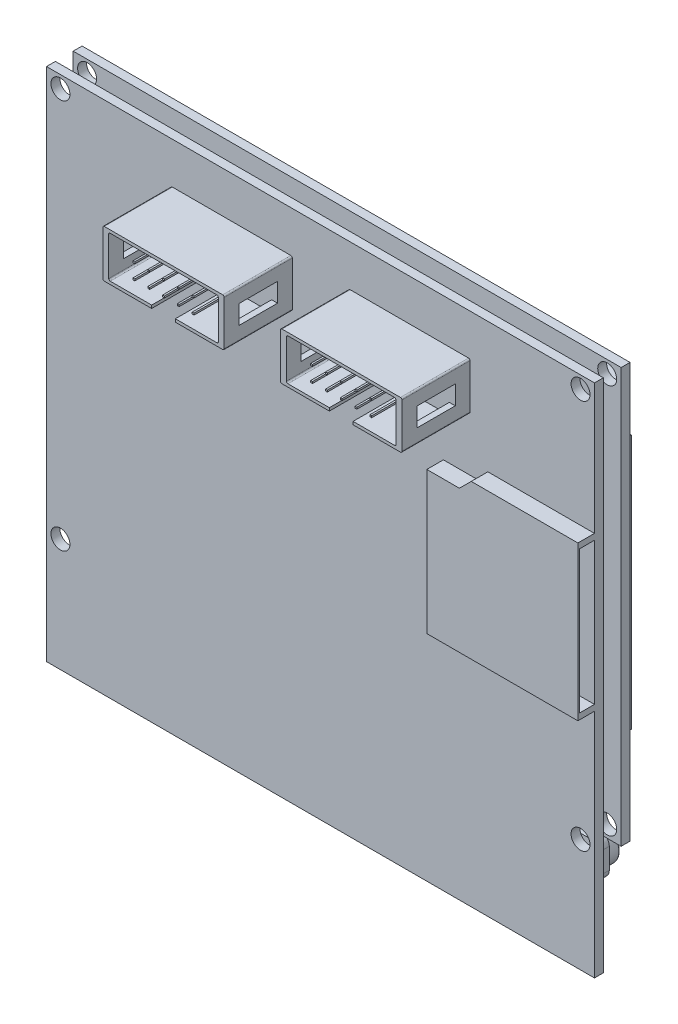
SolidWorks part; units mm, degrees
material "ABS"
ref_plane "Front Plane" through (0, 0, 0) normal (0, 0, 1) x (1, 0, 0)
ref_plane "Top Plane" through (0, 0, 0) normal (0, 1, 0) x (1, 0, 0)
ref_plane "Right Plane" through (0, 0, 0) normal (1, 0, 0) x (0, 0, -1)
sketch "Skica1" plane through (0, 0, 0) normal (0, 0, 1) x (1, 0, 0)
  line L1 (0, 0) -> (92.5, 0)
  line L2 (0, 0) -> (0, 87)
  line L3 (0, 87) -> (92.5, 87)
  line L4 (92.5, 0) -> (92.5, 87)
  dimension "D1" = 87
  dimension "D2" = 92.5
extrude "Přidat vysunutím1" add sketch "Skica1" along normal blind 1.5
ref_plane "Rovina1" through (0, 0, -3) normal (0, 0, -1) x (-1, 0, 0)
sketch "Skica2" plane through (0, 0, -3) normal (0, 0, -1) x (-1, 0, 0)
  line L0 (0, 87) -> (0, 0) construction
  line L1 (-92.5, 87) -> (0, 87)
  line L2 (-92.5, 87) -> (-92.5, 17)
  line L3 (-92.5, 17) -> (0, 17)
  line L4 (0, 87) -> (0, 17)
  dimension "D1" = 70
extrude "Přidat vysunutím2" add sketch "Skica2" along normal blind 1.5 separate body
sketch "Skica3" plane through (0, 0, -4.5) normal (0, 0, -1) x (-1, 0, 0)
  line L0 (-46.25, 87) -> (-46.25, 17) construction
  line L1 (0, 87) -> (-92.5, 87) construction
  line L2 (-92.5, 17) -> (0, 17) construction
  line L3 (-92.5, 52) -> (0, 52) construction
  line L4 (-92.5, 87) -> (-92.5, 17) construction
  line L5 (0, 17) -> (0, 87) construction
  line L6 (-90.15, 84.9) -> (-2.35, 84.9) construction
  line L7 (-2.35, 84.9) -> (-46.25, 52) construction
  line L8 (-46.25, 52) -> (-90.15, 84.9) construction
  circle A0 centre (-90.15, 84.9) radius 1.6
  circle A1 centre (-2.35, 84.9) radius 1.6
  circle A2 centre (-2.35, 19.1) radius 1.6
  circle A3 centre (-90.15, 19.1) radius 1.6
  dimension "D1" = 3.2
  dimension "D2" = 87.8
  dimension "D3" = 65.8
extrude "Odebrat vysunutím1" cut sketch "Skica3" against normal blind 24
sketch "Skica4" plane through (0, 0, -4.5) normal (0, 0, -1) x (-1, 0, 0)
  line L0 (-92.5, 87) -> (0, 17) construction
  line L2 (-84.75, 77.5) -> (-7.75, 77.5)
  line L3 (-84.75, 77.5) -> (-84.75, 26.5)
  line L4 (-84.75, 26.5) -> (-7.75, 26.5)
  line L5 (-7.75, 77.5) -> (-7.75, 26.5)
  line L6 (-84.75, 77.5) -> (-7.75, 26.5) construction
  line L7 (-84.75, 26.5) -> (-7.75, 77.5) construction
  point P4 (-46.25, 52)
  dimension "D1" = 77
  dimension "D2" = 51
extrude "Přidat vysunutím3" add sketch "Skica4" along normal blind 8
sketch "Skica5" plane through (0, 0, -12.5) normal (0, 0, -1) x (-1, 0, 0)
  line L0 (-7.75, 77.5) -> (-84.75, 77.5) construction
  line L1 (-82.75, 72.5) -> (-9.75, 72.5)
  line L2 (-82.75, 72.5) -> (-82.75, 31.5)
  line L3 (-82.75, 31.5) -> (-9.75, 31.5)
  line L4 (-9.75, 72.5) -> (-9.75, 31.5)
  line L5 (-82.75, 72.5) -> (-9.75, 31.5) construction
  line L6 (-82.75, 31.5) -> (-9.75, 72.5) construction
  line L7 (-7.75, 26.5) -> (-7.75, 77.5) construction
  line L8 (-84.75, 26.5) -> (-7.75, 26.5) construction
  line L9 (-84.75, 77.5) -> (-84.75, 26.5) construction
  point P0 (-46.25, 52)
  dimension "D1" = 5
  dimension "D2" = 2
  dimension "D3" = 5
  dimension "D4" = 2
extrude "Odebrat vysunutím2" cut sketch "Skica5" against normal blind 1
fillet "Zaoblit1" radius 0.5 8 edges at (7.75, 77.5, -8.5) (46.25, 77.5, -12.5) (84.75, 77.5, -8.5) (84.75, 52, -12.5) (84.75, 26.5, -8.5) (7.75, 52, -12.5) (7.75, 26.5, -8.5) (46.25, 26.5, -12.5)
sketch "Skica6" plane through (0, 0, -4.5) normal (0, 0, -1) x (-1, 0, 0)
  line L0 (-92.5, 17) -> (0, 17) construction
  line L1 (-78.5, 19.5) -> (-78, 19.5)
  line L2 (-78.5, 19.5) -> (-78.5, 19)
  line L3 (-78.5, 19) -> (-78, 19)
  line L4 (-78, 19.5) -> (-78, 19)
  line L5 (-78.5, 19.5) -> (-78, 19) construction
  line L6 (-78.5, 19) -> (-78, 19.5) construction
  line L7 (-92.5, 87) -> (-92.5, 17) construction
  point P0 (-78.25, 19.25)
  dimension "D1" = 0.5
  dimension "D2" = 2
  dimension "D3" = 14
extrude "Přidat vysunutím4" add sketch "Skica6" along normal blind 4
pattern_linear "LinPole1" count 20 spacing 2.5 along (-1, 0, 0) of "Přidat vysunutím4"
sketch "Skica7" plane through (0, 0, -4.5) normal (0, 0, -1) x (-1, 0, 0)
  line L0 (0, 17) -> (0, 87) construction
  line L5 (-92.5, 52) -> (0, 52) construction
  line L6 (-92.5, 87) -> (-92.5, 17) construction
  circle A0 centre (-2.35, 84.9) radius 2.9
  circle A1 centre (-90.15, 84.9) radius 2.9
  circle A2 centre (-2.35, 19.1) radius 2.9
  circle A3 centre (-90.15, 19.1) radius 2.9
  dimension "D1" = 5.25
  dimension "D2" = 5.25
split line "Rozdělovací křivka1"
fillet "Zaoblit2" radius 1 4 edges at (82.75, 31.5, -12) (9.75, 31.5, -12) (9.75, 72.5, -12) (82.75, 72.5, -12)
sketch "Skica8" plane through (0, 0, -4.5) normal (0, 0, -1) x (-1, 0, 0)
  line L0 (-84.75, 77) -> (-84.75, 27) construction
  line L1 (-84.75, 73.5) -> (-89.75, 73.5)
  line L2 (-84.75, 73.5) -> (-84.75, 30.5)
  line L3 (-84.75, 30.5) -> (-89.75, 30.5)
  line L4 (-89.75, 73.5) -> (-89.75, 30.5)
  line L6 (-8.25, 77.5) -> (-84.25, 77.5) construction
  line L7 (-84.25, 26.5) -> (-8.25, 26.5) construction
  dimension "D1" = 5
  dimension "D2" = 4
  dimension "D3" = 4
extrude "Přidat vysunutím5" add sketch "Skica8" along normal blind 3
sketch "Skica9" plane through (0, 0, 1.5) normal (0, 0, 1) x (1, 0, 0)
  line L0 (92.5, 65) -> (74.5, 65)
  line L1 (92.5, 0) -> (92.5, 87) construction
  line L2 (74.5, 65) -> (72.5, 63)
  line L3 (72.5, 63) -> (67, 63)
  line L4 (67, 63) -> (67, 39)
  line L5 (67, 39) -> (92.5, 39)
  line L6 (92.5, 39) -> (92.5, 65)
  line L7 (92.5, 87) -> (0, 87) construction
  dimension "D1" = 25.5
  dimension "D2" = 22
  dimension "D3" = 26
  dimension "D4" = 2
  dimension "D5" = 5.5
  dimension "D6" = 18
extrude "Přidat vysunutím6" add sketch "Skica9" along normal blind 2.8
ref_plane "Rovina2" through (0, 0, 4.05) normal (0, 0, 1) x (1, 0, 0)
sketch "Skica10" plane through (0, 0, 4.05) normal (0, 0, 1) x (1, 0, 0)
  line L1 (91.5, 64) -> (74.9142, 64)
  line L2 (74.9142, 64) -> (72.9142, 62)
  line L3 (72.9142, 62) -> (68, 62)
  line L4 (68, 62) -> (68, 40)
  line L5 (68, 40) -> (91.5, 40)
  line L6 (92.5, 39) -> (92.5, 65)
  line L7 (92.5, 65) -> (74.5, 65)
  line L8 (74.5, 65) -> (72.5, 63)
  line L9 (72.5, 63) -> (67, 63)
  line L10 (67, 63) -> (67, 39)
  line L11 (67, 39) -> (92.5, 39)
  line L12 (92.5, 39) -> (92.5, 65) construction
  line L13 (92.5, 65) -> (74.5, 65) construction
  line L14 (74.5, 65) -> (72.5, 63) construction
  line L15 (72.5, 63) -> (67, 63) construction
  line L16 (67, 63) -> (67, 39) construction
  line L17 (67, 39) -> (92.5, 39) construction
  line L18 (91.5, 64) -> (93.1112, 64)
  line L19 (93.1112, 64) -> (93.1112, 40)
  line L20 (93.1112, 40) -> (91.5, 40)
  line L27 (91.5, 40) -> (91.5, 64) construction
  dimension "D1" = 0
  dimension "D2" = 1
extrude "Odebrat vysunutím3" cut sketch "Skica10" against normal up to surface (2.55 mm away) up to face at (88.55, 19.1, 1.5)
sketch "Skica12" plane through (0, 0, 1.5) normal (0, 0, 1) x (1, 0, 0)
  line L0 (0, 87) -> (0, 0) construction
  line L1 (21, 80) -> (41.5, 80)
  line L2 (21, 80) -> (21, 72)
  line L3 (21, 72) -> (41.5, 72)
  line L4 (41.5, 80) -> (41.5, 72)
  line L5 (21, 80) -> (41.5, 72) construction
  line L6 (21, 72) -> (41.5, 80) construction
  line L11 (92.5, 87) -> (0, 87) construction
  point P0 (31.25, 76)
  dimension "D1" = 21
  dimension "D2" = 20.5
  dimension "D3" = 8
  dimension "D4" = 7
extrude "Přidat vysunutím7" add sketch "Skica12" along normal blind 2.5
sketch "Skica13" plane through (0, 0, 4) normal (0, 0, 1) x (1, 0, 0)
  line L0 (41.5, 80) -> (21, 80) construction
  line L1 (21, 80) -> (41.5, 80)
  line L2 (21, 80) -> (21, 72)
  line L3 (21, 72) -> (29.25, 72)
  line L4 (41.5, 80) -> (41.5, 72)
  line L5 (21, 80) -> (41.5, 72) construction
  line L6 (21, 72) -> (41.5, 80) construction
  line L7 (21, 80) -> (21, 72) construction
  line L8 (33.25, 72.5) -> (40.5, 72.5)
  line L9 (22, 79.5) -> (40.5, 79.5)
  line L10 (22, 79.5) -> (22, 72.5)
  line L11 (22, 72.5) -> (29.25, 72.5)
  line L12 (40.5, 79.5) -> (40.5, 72.5)
  line L13 (22, 79.5) -> (40.5, 72.5) construction
  line L14 (22, 72.5) -> (40.5, 79.5) construction
  line L16 (29.25, 72.5) -> (29.25, 72)
  line L18 (33.25, 72.5) -> (33.25, 72)
  line L19 (29.25, 72.25) -> (33.25, 72.25) construction
  line L20 (31.25, 72.25) -> (31.25, 76) construction
  line L21 (33.25, 72) -> (41.5, 72)
  line L22 (22, 76) -> (40.5, 76) construction
  line L23 (26.1, 77.4) -> (26.4, 77.4)
  line L24 (26.1, 77.4) -> (26.1, 77.1)
  line L25 (26.1, 77.1) -> (26.4, 77.1)
  line L26 (26.4, 77.4) -> (26.4, 77.1)
  line L27 (26.1, 77.4) -> (26.4, 77.1) construction
  line L28 (26.1, 77.1) -> (26.4, 77.4) construction
  line L29 (28.6, 77.1) -> (28.9, 77.1)
  line L30 (28.6, 77.4) -> (28.6, 77.1)
  line L31 (28.6, 77.4) -> (28.9, 77.4)
  line L32 (28.9, 77.4) -> (28.9, 77.1)
  line L33 (31.1, 77.1) -> (31.4, 77.1)
  line L34 (31.1, 77.4) -> (31.1, 77.1)
  line L35 (31.1, 77.4) -> (31.4, 77.4)
  line L36 (31.4, 77.4) -> (31.4, 77.1)
  line L37 (33.6, 77.1) -> (33.9, 77.1)
  line L38 (33.6, 77.4) -> (33.6, 77.1)
  line L39 (33.6, 77.4) -> (33.9, 77.4)
  line L40 (33.9, 77.4) -> (33.9, 77.1)
  line L41 (36.1, 77.1) -> (36.4, 77.1)
  line L42 (36.1, 77.4) -> (36.1, 77.1)
  line L43 (36.1, 77.4) -> (36.4, 77.4)
  line L44 (36.4, 77.4) -> (36.4, 77.1)
  line L45 (26.1, 77.25) -> (36.4, 77.25) construction
  line L46 (31.25, 76) -> (31.25, 77.25) construction
  line L47 (26.1, 74.9) -> (26.4, 74.6) construction
  line L48 (26.1, 74.6) -> (26.4, 74.9) construction
  line L49 (36.4, 74.6) -> (36.4, 74.9)
  line L50 (36.1, 74.6) -> (36.4, 74.6)
  line L51 (36.1, 74.6) -> (36.1, 74.9)
  line L52 (36.1, 74.9) -> (36.4, 74.9)
  line L53 (33.9, 74.6) -> (33.9, 74.9)
  line L54 (33.6, 74.6) -> (33.9, 74.6)
  line L55 (33.6, 74.6) -> (33.6, 74.9)
  line L56 (33.6, 74.9) -> (33.9, 74.9)
  line L57 (31.4, 74.6) -> (31.4, 74.9)
  line L58 (31.1, 74.6) -> (31.4, 74.6)
  line L59 (31.1, 74.6) -> (31.1, 74.9)
  line L60 (31.1, 74.9) -> (31.4, 74.9)
  line L61 (28.9, 74.6) -> (28.9, 74.9)
  line L62 (28.6, 74.6) -> (28.9, 74.6)
  line L63 (28.6, 74.6) -> (28.6, 74.9)
  line L64 (28.6, 74.9) -> (28.9, 74.9)
  line L65 (26.4, 74.6) -> (26.4, 74.9)
  line L66 (26.1, 74.9) -> (26.4, 74.9)
  line L67 (26.1, 74.6) -> (26.1, 74.9)
  line L68 (26.1, 74.6) -> (26.4, 74.6)
  point P0 (31.25, 76)
  point P12 (31.25, 76)
  point P23 (26.25, 77.25)
  point P51 (26.25, 77.1)
  point P52 (28.75, 77.1)
  point P73 (26.25, 74.75)
  dimension "D1" = 7
  dimension "D2" = 18.5
  dimension "D3" = 4
  dimension "D4" = 0.3
  dimension "D5" = 1.25
  dimension "D7" = 2.5
  dimension "D6" = 5
extrude "Přidat vysunutím8" add sketch "Skica13" along normal blind 9
fillet "Zaoblit3" radius 0.25 8 edges at (40.5, 72.5, 8.5) (40.5, 79.5, 8.5) (22, 72.5, 8.5) (22, 79.5, 8.5) (21, 80, 7.25) (21, 72, 7.25) (41.5, 80, 7.25) (41.5, 72, 7.25)
pattern_linear "LinPole2" count 2 spacing 30 along (1, 0, 0) of "Přidat vysunutím7", "Přidat vysunutím8"
fillet "Zaoblit4" radius 0.25 8 edges at (71.5, 72, 7.25) (71.5, 80, 7.25) (51, 80, 7.25) (51, 72, 7.25) (52, 72.5, 8.5) (52, 79.5, 8.5) (70.5, 79.5, 8.5) (70.5, 72.5, 8.5)
sketch "Skica14" plane through (0, 0, 0) normal (0, 0, -1) x (-1, 0, 0)
  line L0 (0, 87) -> (0, 0) construction
  line L1 (-16, 14.5) -> (-4, 14.5)
  line L2 (-16, 14.5) -> (-16, 2.5)
  line L3 (-16, 2.5) -> (-4, 2.5)
  line L4 (-4, 14.5) -> (-4, 2.5)
  line L5 (0, 0) -> (-92.5, 0) construction
  line L6 (-88.15, 17) -> (-4.35, 17) construction
  dimension "D1" = 12
  dimension "D2" = 4
  dimension "D3" = 2.5
  dimension "D4" = 2.5
extrude "Přidat vysunutím9" add sketch "Skica14" along normal blind 6.5
sketch "Skica15" plane through (0, 0, -6.5) normal (0, 0, -1) x (-1, 0, 0)
  line L0 (-16, 14.5) -> (-4, 2.5) construction
  circle A0 centre (-10, 8.5) radius 3
  dimension "D1" = 6
extrude "Přidat vysunutím10" add sketch "Skica15" along normal blind 6
sketch "Skica16" plane through (0, 0, -12.5) normal (0, 0, -1) x (-1, 0, 0)
  circle A0 centre (-10, 8.5) radius 7.5
  dimension "D1" = 15
extrude "Přidat vysunutím11" add sketch "Skica16" along normal blind 15
ref_plane "Rovina3" through (17.5, 0, 0) normal (1, 0, 0) x (0, 0, -1)
ref_plane "Rovina4" through (10, 0, 0) normal (1, 0, 0) x (0, 0, -1)
sketch "Skica17" plane through (10, 0, 0) normal (1, 0, 0) x (0, 0, -1)
  line L0 (12.5, 8.5) -> (27.5, 8.5) construction
  line L1 (12.5, 16) -> (12.5, 1) construction
  line L2 (27.5, 1) -> (27.5, 16) construction
  line L3 (14.5, 16) -> (15, 14.5)
  line L4 (27.5, 16) -> (12.5, 16) construction
  line L5 (15, 14.5) -> (27.5, 14)
  line L6 (27.5, 14) -> (27.5, 16)
  line L7 (27.5, 16) -> (14.5, 16)
  dimension "D1" = 11
  dimension "D2" = 2
  dimension "D3" = 0.5
  dimension "D4" = 12
revolve "Odebrat rotací1" cut sketch "Skica17" angle 360 about L0
sketch "Skica18" plane through (0, 0, -27.5) normal (0, 0, -1) x (-1, 0, 0)
  line L0 (-10, 7.975) -> (-10, -7.975) construction
  line L1 (-10.5, 8.5) -> (-9.5, 8.5)
  line L2 (-10.5, 8.5) -> (-10.5, 15.9833)
  line L3 (-10.5, 15.9833) -> (-9.5, 15.9833)
  line L4 (-9.5, 8.5) -> (-9.5, 15.9833)
  line L5 (-10.5, 8.5) -> (-9.5, 15.9833) construction
  line L6 (-10.5, 15.9833) -> (-9.5, 8.5) construction
  line L7 (-10, 8.5) -> (-4.5, 8.5) construction
  circle A0 centre (-10, 8.5) radius 7.5 construction
  circle A1 centre (-10, 8.5) radius 5.5 construction
  point P0 (-10, 12.2417)
  dimension "D1" = 1
extrude "Přidat vysunutím12" add sketch "Skica18" along normal blind 0.1 and the other way blind 15
sketch "Skica19" plane through (0, 0, -27.5) normal (0, 0, -1) x (-1, 0, 0)
  line L0 (-10.5, 8.5) -> (-9.5, 8.5) construction
  line L5 (-9.5, 8.5) -> (-9.5, 15.9833)
  line L6 (-9.5, 15.9833) -> (-10.5, 15.9833)
  line L7 (-10.5, 15.9833) -> (-10.5, 8.5)
  line L8 (-10.5, 8.5) -> (-9.5, 8.5)
  line L9 (-9.5, 8.5) -> (-9.5, 13.7)
  line L11 (-10.5, 13.7) -> (-10.5, 8.5)
  line L12 (-10.5, 8.5) -> (-9.5, 8.5)
  arc A0 (-10.5, 13.7) -> (-9.5, 13.7) centre (-10, 8.5) ccw
  dimension "D2" = 5.2
  dimension "D1" = 0
split line "Rozdělovací křivka2"
chamfer "Zkosení1" distance 13 angle 3 1 edges at (10, 15.9833, -27.6)
fillet "Zaoblit5" radius 0.2 4 edges at (10, 3, -27.5) (9.5, 15.6427, -21.1) (10.5, 15.6427, -21.1) (10, 15.302, -27.6)
sketch "Skica20" plane through (0, 0, 0) normal (0, 0, -1) x (-1, 0, 0)
  line L0 (-16, 14.5) -> (-16, 2.5) construction
  circle A0 centre (-27.5, 8.5) radius 5.5
  arc A2 (-10.5, 13.7842) -> (-9.5, 13.7842) centre (-10, 8.5) ccw construction
  dimension "D2" = 11
  dimension "D1" = 6
  dimension "D3" = 0
extrude "Přidat vysunutím13" add sketch "Skica20" along normal blind 9
fillet "Zaoblit6" radius 0.5 1 edges at (22, 8.5, -9)
sketch "Skica21" plane through (0, 0, -9) normal (0, 0, -1) x (-1, 0, 0)
  circle A0 centre (-27.5, 8.5) radius 1
  dimension "D1" = 2
extrude "Odebrat vysunutím4" cut sketch "Skica21" against normal blind 5
sketch "Skica22" plane through (0, 0, 0) normal (0, 0, -1) x (-1, 0, 0)
  line L0 (-16, 14.5) -> (-16, 2.5) construction
  line L1 (-46, 11.5) -> (-40, 11.5)
  line L2 (-46, 11.5) -> (-46, 5.5)
  line L3 (-46, 5.5) -> (-40, 5.5)
  line L4 (-40, 11.5) -> (-40, 5.5)
  line L5 (-46, 11.5) -> (-40, 5.5) construction
  line L6 (-46, 5.5) -> (-40, 11.5) construction
  line L7 (-27.5, 8.5) -> (-64.2469, 8.5) construction
  point P0 (-43, 8.5)
  dimension "D1" = 6
  dimension "D2" = 24
extrude "Přidat vysunutím14" add sketch "Skica22" along normal blind 4
sketch "Skica23" plane through (0, 0, -4) normal (0, 0, -1) x (-1, 0, 0)
  line L0 (-46, 8.5) -> (-40, 8.5) construction
  line L1 (-46, 11.5) -> (-46, 5.5) construction
  line L2 (-40, 5.5) -> (-40, 11.5) construction
  circle A0 centre (-43, 8.5) radius 1.5
  dimension "D1" = 3
extrude "Přidat vysunutím15" add sketch "Skica23" along normal blind 1.5
fillet "Zaoblit7" radius 0.1 1 edges at (41.5, 8.5, -5.5)
ref_plane "Rovina5" through (0, 0, -4) normal (0, 0, -1) x (-1, 0, 0)
sketch "Skica24" plane through (0, 0, -4) normal (0, 0, -1) x (-1, 0, 0)
  line L0 (0, 0) -> (-92.5, 0) construction
  line L1 (-87.5, 14.5) -> (-80.5, 14.5)
  line L2 (-87.5, 14.5) -> (-87.5, 8)
  line L3 (-87.5, 8) -> (-80.5, 8)
  line L4 (-80.5, 14.5) -> (-80.5, 8)
  line L5 (-87.5, 14.5) -> (-80.5, 8) construction
  line L6 (-87.5, 8) -> (-80.5, 14.5) construction
  line L7 (-92.5, 0) -> (-92.5, 87) construction
  point P0 (-84, 11.25)
  dimension "D1" = 6.5
  dimension "D2" = 7
  dimension "D3" = 8
  dimension "D4" = 5
extrude "Přidat vysunutím16" add sketch "Skica24" along normal blind 2 separate body
fillet "Zaoblit8" radius 1.5 2 edges at (87.5, 14.5, -5) (87.5, 8, -5)
sketch "Skica25" plane through (0, 0, -6) normal (0, 0, -1) x (-1, 0, 0)
  line L0 (-80.5, 11.25) -> (-87.3, 11.25) construction
  line L1 (-80.5, 8) -> (-80.5, 14.5) construction
  line L2 (-87.5, 13) -> (-87.5, 9.5) construction
  line L4 (-84.8, 13.5) -> (-83.8, 13.5)
  line L5 (-84.8, 13.5) -> (-84.8, 9)
  line L6 (-84.8, 9) -> (-83.8, 9)
  line L7 (-83.8, 13.5) -> (-83.8, 9)
  line L8 (-84.8, 13.5) -> (-83.8, 9) construction
  line L9 (-84.8, 9) -> (-83.8, 13.5) construction
  circle A0 centre (-84.3, 11.25) radius 3
  dimension "D1" = 6
  dimension "D2" = 3.2
  dimension "D3" = 1
  dimension "D4" = 4.5
extrude "Přidat vysunutím17" add sketch "Skica25" along normal blind 2
fillet "Zaoblit9" radius 0.2 1 edges at (81.3, 11.25, -8)
sketch "Skica26" plane through (16, 0, 0) normal (1, 0, 0) x (0, 0, -1)
  line L0 (6.5, 14.5) -> (0, 14.5) construction
  line L1 (0, 2.5) -> (2.5, 2.5)
  line L2 (0, 2.5) -> (0, 14.5)
  line L3 (0, 14.5) -> (2.5, 14.5)
  line L4 (2.5, 2.5) -> (2.5, 14.5)
  dimension "D1" = 2.5
split line "Rozdělovací křivka3"
sketch "Skica27" plane through (4, 0, 0) normal (-1, 0, 0) x (0, 0, 1)
  line L0 (-6.5, 2.5) -> (0, 2.5) construction
  line L1 (0, 14.5) -> (-2.5, 14.5)
  line L2 (0, 14.5) -> (0, 2.5)
  line L3 (0, 2.5) -> (-2.5, 2.5)
  line L4 (-2.5, 14.5) -> (-2.5, 2.5)
  dimension "D1" = 2.5
split line "Rozdělovací křivka4"
ref_plane "Rovina6" through (87, 0, 0) normal (1, 0, 0) x (0, 0, -1)
sketch "Skica28" plane through (87, 0, 0) normal (1, 0, 0) x (0, 0, -1)
  line L0 (4, 13) -> (4, 9.5) construction
  line L1 (4, 12.25) -> (0, 12.25)
  line L2 (4, 12.25) -> (4, 10.25)
  line L3 (4, 10.25) -> (0, 10.25)
  line L4 (0, 12.25) -> (0, 10.25)
  line L5 (0, 11.5) -> (0, 5.5) construction
  line L6 (4, 11.25) -> (6, 11.25) construction
  line L7 (6, 13) -> (6, 9.5) construction
  dimension "D1" = 2
extrude "Přidat vysunutím18" add sketch "Skica28" along normal blind 0.1
ref_plane "Rovina7" through (0, 11.25, 0) normal (0, -1, 0) x (-1, 0, 0)
ref_plane "Rovina8" through (0, 10.25, 0) normal (0, -1, 0) x (-1, 0, 0)
sketch "Skica29" plane through (0, 10.25, 0) normal (0, -1, 0) x (-1, 0, 0)
  line L0 (-80.5, 5) -> (-80.4, 5)
  line L1 (-80.5, 6) -> (-80.5, 4) construction
  line L2 (-80.4, 5) -> (-80.4, 1.4)
  line L3 (-80.4, 1.4) -> (-81.8, 1.4)
  line L4 (-81.8, 1.4) -> (-81.8, 0)
  line L5 (0, 0) -> (-92.5, 0) construction
  line L6 (-81.8, 0) -> (-81.9, 0)
  line L7 (-81.9, 0) -> (-81.9, 1.5)
  line L8 (-81.9, 1.5) -> (-80.5, 1.5)
  line L9 (-80.5, 1.5) -> (-80.5, 4)
  line L10 (-80.5, 5) -> (-80.5, 4)
  dimension "D1" = 0.1
  dimension "D2" = 0.1
  dimension "D3" = 0.1
  dimension "D4" = 1.5
  dimension "D5" = 1.4
extrude "Přidat vysunutím19" add sketch "Skica29" along normal blind 2
mirror "Zrcadlit1" about plane through (0, 11.25, 0) normal (0, -1, 0) of "Přidat vysunutím19"
sketch "Skica30" plane through (21, 0, 0) normal (-1, 0, 0) x (0, 0, 1)
  line L0 (4, 72.75) -> (4, 79.25) construction
  line L1 (4, 77.6) -> (10.5, 77.6)
  line L2 (4, 77.6) -> (4, 74.4)
  line L3 (4, 74.4) -> (10.5, 74.4)
  line L4 (10.5, 77.6) -> (10.5, 74.4)
  line L5 (13, 77.4) -> (4, 77.4) construction
  line L6 (13, 74.6) -> (4, 74.6) construction
  line L8 (13, 79.75) -> (13, 72.25) construction
  dimension "D1" = 0.2
  dimension "D2" = 0.2
  dimension "D3" = 2.5
extrude "Odebrat vysunutím5" cut sketch "Skica30" against normal up to surface (1 mm away) up to face at (22, 76, 8.5)
ref_plane "Rovina9" through (31.25, 0, 0) normal (-1, 0, 0) x (0, 0, 1)
sketch "Skica31" plane through (41.5, 0, 0) normal (1, 0, 0) x (0, 0, -1)
  line L1 (-10.5, 77.6) -> (-4, 77.6)
  line L2 (-10.5, 77.6) -> (-10.5, 74.4)
  line L3 (-10.5, 74.4) -> (-4, 74.4)
  line L4 (-4, 77.6) -> (-4, 74.4)
extrude "Odebrat vysunutím6" cut sketch "Skica31" against normal up to surface (1 mm away) up to face at (40.5, 76, 8.5)
sketch "Skica32" plane through (71.5, 0, 0) normal (1, 0, 0) x (0, 0, -1)
  line L1 (-10.5, 77.6) -> (-4, 77.6)
  line L2 (-10.5, 77.6) -> (-10.5, 74.4)
  line L3 (-10.5, 74.4) -> (-4, 74.4)
  line L4 (-4, 77.6) -> (-4, 74.4)
extrude "Odebrat vysunutím7" cut sketch "Skica32" against normal up to surface (1 mm away) up to face at (70.5, 76, 8.5)
sketch "Skica33" plane through (51, 0, 0) normal (-1, 0, 0) x (0, 0, 1)
  line L1 (10.5, 77.6) -> (4, 77.6)
  line L2 (10.5, 77.6) -> (10.5, 74.4)
  line L3 (10.5, 74.4) -> (4, 74.4)
  line L4 (4, 77.6) -> (4, 74.4)
extrude "Odebrat vysunutím8" cut sketch "Skica33" against normal up to surface (1 mm away) up to face at (52, 76, 8.5)
